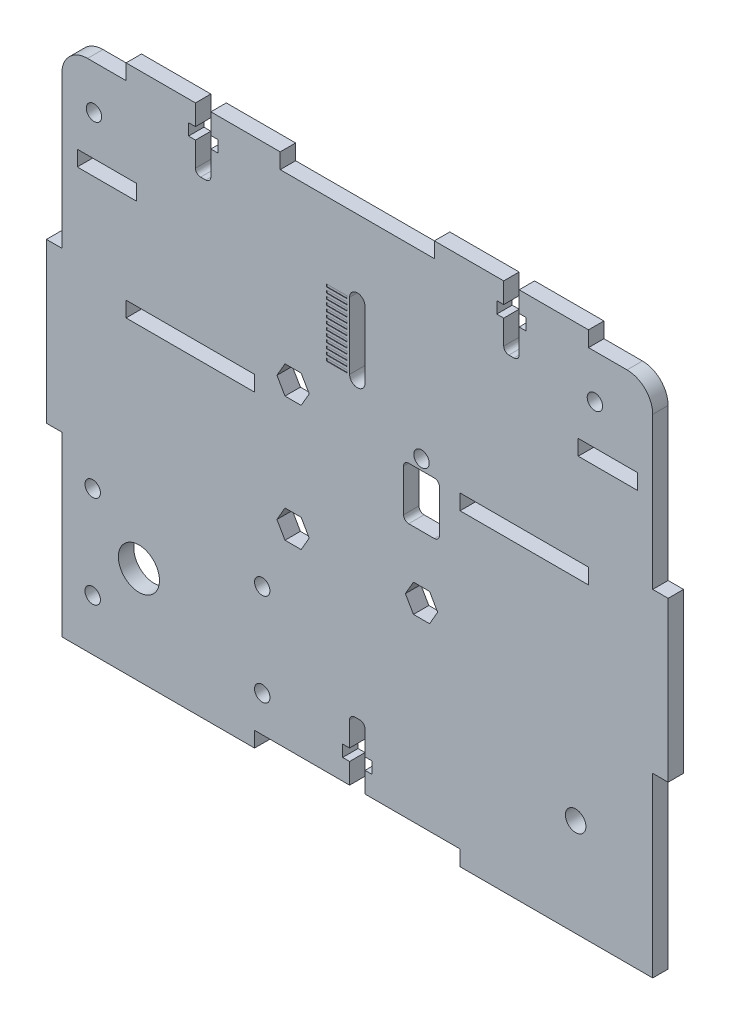
SolidWorks part; units mm, degrees
other "Marcação1"
sketch "Esboço7" plane through (-68, 31.5, 3) normal (-0.6758, 0.2828, 0.6807) x (0.7271, 0.1043, 0.6785)
sketch "Esboço8" plane through (-68, 31.5, 3) normal (-0.6758, 0.2828, 0.6807) x (0.7271, 0.1043, 0.6785)
sketch "Esboço9" plane through (-68, 31.5, 3) normal (-0.6758, 0.2828, 0.6807) x (0.7271, 0.1043, 0.6785)
sketch "Esboço10" plane through (-68, 31.5, 3) normal (-0.6758, 0.2828, 0.6807) x (0.7271, 0.1043, 0.6785)
sketch "Esboço11" plane through (-68, 36.25, 3) normal (-0.6758, 0.2828, 0.6807) x (0.7271, 0.1043, 0.6785)
sketch "Esboço13" plane through (-68, 36.25, 3) normal (-0.6758, 0.2828, 0.6807) x (0.7271, 0.1043, 0.6785)
sketch "Esboço15" plane through (-68, 36.25, 3) normal (-0.6758, 0.2828, 0.6807) x (0.7271, 0.1043, 0.6785)
sketch "Esboço19" plane through (-68, 66.25, 3) normal (-0.6758, 0.2828, 0.6807) x (0.7271, 0.1043, 0.6785)
sketch "Esboço22" plane through (-68, 95.5577, 3) normal (-0.6758, 0.2828, 0.6807) x (0.7271, 0.1043, 0.6785)
sketch "Sketch18" plane through (-60.5, 53, 1.5) normal (-0.6758, 0.2828, 0.6807) x (0.7271, 0.1043, 0.6785)
sketch "Sketch19" plane through (-60.5, 53, 1.5) normal (-0.6758, 0.2828, 0.6807) x (0.7271, 0.1043, 0.6785)
sketch "Sketch21" plane through (-60.5, 53, 1.5) normal (-0.6758, 0.2828, 0.6807) x (0.7271, 0.1043, 0.6785)
material "Acrylic (Medium-high impact)"
ref_plane "Plano frontal" through (0, 0, 0) normal (0, 0, 1) x (1, 0, 0)
ref_plane "Plano superior" through (0, 0, 0) normal (0, 1, 0) x (1, 0, 0)
ref_plane "Plano direito" through (0, 0, 0) normal (1, 0, 0) x (0, 0, -1)
sketch "Esboço1" plane through (0, 0, 0) normal (0, 0, 1) x (1, 0, 0)
  line L6 (57.5, -50) -> (-57.5, -50)
  line L8 (57.5, -50) -> (57.5, 50)
  line L9 (57.5, 50) -> (-57.5, 50)
  line L10 (-57.5, -50) -> (-57.5, 50)
  line L11 (57.5, -50) -> (-57.5, 50) construction
  line L12 (57.5, 50) -> (-57.5, -50) construction
  point P0 (0, 0)
  dimension "D1" = 100
  dimension "D2" = 115
extrude "Ressalto-extrusão1" add sketch "Esboço1" along normal mid plane 3
sketch "Esboço2" plane through (0, 0, 1.5) normal (0, 0, 1) x (1, 0, 0)
  line L1 (-20, -50) -> (20, -50)
  line L2 (-20, -50) -> (-20, -47)
  line L3 (-20, -47) -> (20, -47)
  line L4 (20, -50) -> (20, -47)
  line L6 (-57.5, -50) -> (57.5, -50) construction
  line L25 (57.5, 50) -> (-57.5, 50) construction
  line L26 (-45, 13) -> (-20, 13)
  line L29 (-45, 13) -> (-45, 10)
  line L30 (-45, 10) -> (-20, 10)
  line L31 (-20, 13) -> (-20, 10)
  line L32 (0, -1.65) -> (0, 1.65) construction
  line L33 (20, 13) -> (20, 10)
  line L34 (45, 10) -> (20, 10)
  line L35 (45, 13) -> (45, 10)
  line L36 (45, 13) -> (20, 13)
  point P6 (0, -47)
  dimension "D4" = 3
  dimension "D5" = 40
  dimension "D1" = 37
  dimension "D2" = 40
  dimension "D3" = 25
extrude "Corte-extrusão1" cut sketch "Esboço2" against normal through all
sketch "Esboço3" plane through (0, 0, 1.5) normal (0, 0, 1) x (1, 0, 0)
  line L0 (57.5, -50) -> (57.5, 50) construction
  line L1 (57.5, 15.5) -> (60.5, 15.5)
  line L2 (57.5, 15.5) -> (57.5, -15.5)
  line L3 (57.5, -15.5) -> (60.5, -15.5)
  line L4 (60.5, 15.5) -> (60.5, -15.5)
  line L5 (0, -1.65) -> (0, 1.65) construction
  line L6 (-57.5, -15.5) -> (-60.5, -15.5)
  line L7 (-57.5, 15.5) -> (-60.5, 15.5)
  line L8 (-57.5, 15.5) -> (-57.5, -15.5)
  line L9 (-60.5, 15.5) -> (-60.5, -15.5)
  line L10 (57.5, 50) -> (-57.5, 50) construction
  line L11 (-45, 53) -> (-15, 53)
  line L12 (-45, 53) -> (-45, 50)
  line L13 (-45, 50) -> (-15, 50)
  line L14 (-15, 53) -> (-15, 50)
  line L15 (15, 53) -> (15, 50)
  line L16 (45, 50) -> (15, 50)
  line L17 (45, 53) -> (45, 50)
  line L18 (45, 53) -> (15, 53)
  line L19 (0, -37.5) -> (0, 37.5) construction
  line L20 (-57.5, 50) -> (-57.5, -50) construction
  point P6 (57.5, 0)
  point P28 (0, 0)
  dimension "D1" = 3
  dimension "D2" = 31
  dimension "D3" = 3
  dimension "D4" = 30
  dimension "D5" = 12.5
  dimension "D6" = 15
extrude "Ressalto-extrusão2" add sketch "Esboço3" against normal through all
sketch "Esboço30" plane through (0, 0, -1.5) normal (0, 0, -1) x (-1, 0, 0)
  line L0 (60.5, 15.5) -> (60.5, -15.5) construction
  line L1 (57.5, -50) -> (20, -50) construction
  circle A0 centre (42.5, -31) radius 4
  dimension "D1" = 8
  dimension "D2" = 18
  dimension "D3" = 19
extrude "Corte-extrusão11" cut sketch "Esboço30" against normal through all both and the other way through all
sketch "Esboço31" plane through (0, 0, -1.5) normal (0, 0, -1) x (-1, 0, 0)
  circle A4 centre (51.5, -22) radius 1.5
  circle A5 centre (51.5, -40) radius 1.5
  circle A6 centre (42.5, -31) radius 4 construction
  circle A7 centre (18.5, -22) radius 1.5
  circle A8 centre (18.5, -40) radius 1.5
  dimension "D1" = 3
  dimension "D2" = 9
  dimension "D3" = 9
  dimension "D4" = 18
  dimension "D5" = 33
extrude "Corte-extrusão12" cut sketch "Esboço31" against normal through all both and the other way through all
sketch "Esboço4" plane through (0, 0, 1.5) normal (0, 0, 1) x (1, 0, 0)
  line L0 (-46.5, -31) -> (-38.5, -31) construction
  line L61 (-57.5, -15.5) -> (-57.5, -50) construction
  line L65 (57.5, -50) -> (57.5, -15.5) construction
  circle A9 centre (-42.5, -31) radius 4 construction
  circle A13 centre (42.5, -31) radius 2
  point P70 (-42.5, -31)
  dimension "D1" = 15
  dimension "D2" = 4
  dimension "D8" = 15
extrude "Corte-extrusão2" cut sketch "Esboço4" against normal through all
sketch "Sketch5" plane through (0, 0, 0) normal (0, 0, 1) x (1, 0, 0)
  line L0 (20, -47) -> (-20, -47) construction
  line L1 (-1.5, -47) -> (1.5, -47)
  line L2 (-1.5, -47) -> (-1.5, -43)
  line L3 (-0.5, -35) -> (0.5, -35)
  line L4 (1.5, -47) -> (1.5, -43)
  line L5 (1.5, -40.73) -> (2.85, -40.73)
  line L6 (-2.85, -40.73) -> (-1.5, -40.73)
  line L7 (-2.85, -40.73) -> (-2.85, -43)
  line L8 (-2.85, -43) -> (-1.5, -43)
  line L9 (2.85, -40.73) -> (2.85, -43)
  line L10 (-1.5, -40.73) -> (-1.5, -36)
  line L11 (1.5, -43) -> (2.85, -43)
  line L12 (1.5, -40.73) -> (1.5, -36)
  arc A0 (0.5, -35) -> (1.5, -36) centre (0.5, -36) cw
  arc A1 (-1.5, -36) -> (-0.5, -35) centre (-0.5, -36) cw
  point P6 (0, -35)
  point P18 (1.5, -35)
  point P21 (-1.5, -35)
  dimension "D7" = 1
  dimension "D1" = 12
  dimension "D2" = 3
  dimension "D3" = 2.27
  dimension "D4" = 1.35
  dimension "D5" = 1.35
  dimension "D6" = 4
extrude "Cut-Extrude2" cut sketch "Sketch5" against normal through all both and the other way through all
sketch "Sketch8" [suppressed] plane through (0, 0, 1.5) normal (0, 0, 1) x (1, 0, 0)
  line L8 (-57.5, 39.6519) -> (-53.4896, 39.6519)
  line L9 (-58, 31.6519) -> (-58, 23.6519) construction
  line L10 (-57.5, 23.6519) -> (-53.4896, 23.6519)
  line L11 (-45, 36.6519) -> (-45, 26.6519)
  line L12 (-58, 31.6519) -> (-45, 31.6519) construction
  line L13 (-48.5, 41.4019) -> (-50, 44)
  line L14 (-50, 44) -> (-53, 44)
  line L15 (-53, 44) -> (-54.5, 41.4019)
  line L16 (-54.5, 41.4019) -> (-53.4896, 39.6519)
  line L18 (-49.5104, 39.6519) -> (-48.5, 41.4019)
  line L19 (-49.5104, 39.6519) -> (-48, 39.6519)
  line L22 (-53.8581, 38.8038) -> (-52.2318, 38.8038) [skipped]
  line L24 (-49.5104, 23.6519) -> (-48.5, 21.9019)
  line L25 (-54.5, 21.9019) -> (-53.4896, 23.6519)
  line L26 (-53, 19.3038) -> (-54.5, 21.9019)
  line L27 (-50, 19.3038) -> (-53, 19.3038)
  line L28 (-48.5, 21.9019) -> (-50, 19.3038)
  line L29 (-45, 50) -> (-57.5, 50) construction
  line L30 (-57.5, 50) -> (-57.5, 15.5) construction
  line L31 (-57.5, 39.6519) -> (-57.5, 23.6519)
  line L32 (-58, 39.6519) -> (-58, 31.6519) construction
  line L33 (-58, 39.6519) -> (-57.5, 39.6519) construction
  line L34 (-58, 23.6519) -> (-57.5, 23.6519) construction
  line L35 (-49.5104, 23.6519) -> (-48, 23.6519)
  line L36 (0, -1.65) -> (0, 1.65) construction
  line L37 (58, 23.6519) -> (57.5, 23.6519) construction
  line L38 (58, 39.6519) -> (57.5, 39.6519) construction
  line L39 (58, 39.6519) -> (58, 31.6519) construction
  line L40 (58, 31.6519) -> (45, 31.6519) construction
  line L41 (58, 31.6519) -> (58, 23.6519) construction
  line L42 (49.5104, 23.6519) -> (48, 23.6519)
  line L43 (57.5, 39.6519) -> (57.5, 23.6519)
  line L44 (48.5, 21.9019) -> (50, 19.3038)
  line L45 (50, 19.3038) -> (53, 19.3038)
  line L46 (53, 19.3038) -> (54.5, 21.9019)
  line L47 (54.5, 21.9019) -> (53.4896, 23.6519)
  line L48 (49.5104, 23.6519) -> (48.5, 21.9019)
  line L49 (49.5104, 39.6519) -> (48, 39.6519)
  line L50 (49.5104, 39.6519) -> (48.5, 41.4019)
  line L51 (54.5, 41.4019) -> (53.4896, 39.6519)
  line L52 (53, 44) -> (54.5, 41.4019)
  line L53 (50, 44) -> (53, 44)
  line L54 (48.5, 41.4019) -> (50, 44)
  line L55 (45, 36.6519) -> (45, 26.6519)
  line L56 (57.5, 23.6519) -> (53.4896, 23.6519)
  line L57 (57.5, 39.6519) -> (53.4896, 39.6519)
  arc A0 (-49.25, 40.1029) -> (-53.75, 40.1029) centre (-51.5, 41.4019) ccw construction
  arc A1 (-49.25, 23.201) -> (-53.75, 23.201) centre (-51.5, 21.9019) cw construction
  arc A2 (-48, 23.6519) -> (-45, 26.6519) centre (-48, 26.6519) ccw
  arc A3 (-48, 39.6519) -> (-45, 36.6519) centre (-48, 36.6519) cw
  arc A4 (49.25, 23.201) -> (53.75, 23.201) centre (51.5, 21.9019) ccw construction
  arc A5 (49.25, 40.1029) -> (53.75, 40.1029) centre (51.5, 41.4019) cw construction
  arc A6 (48, 39.6519) -> (45, 36.6519) centre (48, 36.6519) ccw
  arc A7 (48, 23.6519) -> (45, 26.6519) centre (48, 26.6519) cw
  point P27 (-51.5, 31.6519)
  point P36 (-45, 23.6519)
  point P39 (-45, 39.6519)
  point P72 (45, 39.6519)
  point P73 (45, 23.6519)
  dimension "D1" = 13
  dimension "D3" = 3
  dimension "D5" = 6
  dimension "D4" = 19.5
  dimension "D6" = 3
  dimension "D7" = 3
  dimension "D8" = 16
extrude "Cut-Extrude6" [suppressed] cut sketch "Sketch8" against normal through all both and the other way through all
fillet "Fillet2" [suppressed] radius 1.5
sketch "Sketch17" plane through (0, 0, 0) normal (0, 0, 1) x (1, 0, 0)
  line L1 (-54.5, 33.7) -> (-43, 33.7)
  line L2 (-54.5, 33.7) -> (-54.5, 30.7)
  line L3 (-54.5, 30.7) -> (-43, 30.7)
  line L4 (-43, 33.7) -> (-43, 30.7)
  line L5 (-45, 50) -> (-57.5, 50) construction
  line L6 (-57.5, 50) -> (-57.5, 15.5) construction
  line L7 (0, -1.65) -> (0, 1.65) construction
  line L8 (43, 33.7) -> (43, 30.7)
  line L9 (54.5, 30.7) -> (43, 30.7)
  line L10 (54.5, 33.7) -> (54.5, 30.7)
  line L11 (54.5, 33.7) -> (43, 33.7)
  circle A0 centre (-51.25, 41.5) radius 1.5
  circle A1 centre (46.25, 41.5) radius 1.5
  point P6 (-48.75, 33.7)
  point P20 (48.75, 33.7)
  dimension "D2" = 3
  dimension "D5" = 7.8
  dimension "D6" = 7
  dimension "D1" = 11.5
  dimension "D3" = 3
  dimension "D4" = 2.5
  dimension "D7" = 3
  dimension "D8" = 2.5
  dimension "D9" = 86
extrude "Corte Gy-53LDK" cut sketch "Sketch17" against normal through all both and the other way through all
sketch "Sketch11" plane through (0, 0, 0) normal (0, 0, 1) x (1, 0, 0)
  line L0 (-15, 53) -> (-45, 53) construction
  line L1 (-31.5, 53) -> (-28.5, 53)
  line L2 (-31.5, 53) -> (-31.5, 49)
  line L3 (-30.5, 41) -> (-29.5, 41)
  line L4 (-28.5, 53) -> (-28.5, 49)
  line L5 (-45, 53) -> (-45, 50) construction
  line L6 (-28.5, 49) -> (-27.15, 49)
  line L7 (-32.85, 49) -> (-31.5, 49)
  line L8 (-32.85, 49) -> (-32.85, 46.73)
  line L9 (-32.85, 46.73) -> (-31.5, 46.73)
  line L10 (-27.15, 49) -> (-27.15, 46.73)
  line L11 (-31.5, 46.73) -> (-31.5, 42)
  line L12 (-28.5, 46.73) -> (-28.5, 42)
  line L13 (-28.5, 46.73) -> (-27.15, 46.73)
  line L14 (0, -1.65) -> (0, 1.65) construction
  line L15 (28.5, 46.73) -> (27.15, 46.73)
  line L16 (28.5, 46.73) -> (28.5, 42)
  line L17 (31.5, 46.73) -> (31.5, 42)
  line L18 (27.15, 49) -> (27.15, 46.73)
  line L19 (32.85, 46.73) -> (31.5, 46.73)
  line L20 (32.85, 49) -> (32.85, 46.73)
  line L21 (32.85, 49) -> (31.5, 49)
  line L22 (28.5, 49) -> (27.15, 49)
  line L23 (28.5, 53) -> (28.5, 49)
  line L24 (30.5, 41) -> (29.5, 41)
  line L25 (31.5, 53) -> (31.5, 49)
  line L26 (31.5, 53) -> (28.5, 53)
  arc A0 (-29.5, 41) -> (-28.5, 42) centre (-29.5, 42) ccw
  arc A1 (-31.5, 42) -> (-30.5, 41) centre (-30.5, 42) ccw
  arc A2 (31.5, 42) -> (30.5, 41) centre (30.5, 42) cw
  arc A3 (29.5, 41) -> (28.5, 42) centre (29.5, 42) cw
  point P12 (-31.5, 41)
  point P39 (31.5, 41)
  dimension "D4" = 1
  dimension "D1" = 3
  dimension "D2" = 12
  dimension "D3" = 13.5
  dimension "D5" = 4
  dimension "D6" = 2.27
  dimension "D7" = 1.35
  dimension "D8" = 1.35
extrude "Cut-Extrude8" cut sketch "Sketch11" against normal through all both and the other way through all
sketch "Sketch16" plane through (0, 0, 0) normal (0, 0, 1) x (1, 0, 0)
  line L3 (15.64, -9.2807) -> (14.07, -6.5614)
  line L4 (10, 13.0193) -> (15, 13.0193)
  line L5 (9, 12.0193) -> (9, 3.8193)
  line L6 (10, 2.8193) -> (15, 2.8193)
  line L7 (16, 12.0193) -> (16, 3.8193)
  line L8 (14.07, -6.5614) -> (10.93, -6.5614)
  line L9 (10.93, -6.5614) -> (9.36, -9.2807)
  line L10 (9.36, -9.2807) -> (10.93, -12)
  line L11 (10.93, -12) -> (14.07, -12)
  line L12 (14.07, -12) -> (15.64, -9.2807)
  line L14 (-9.36, 15.0193) -> (-10.93, 17.7386)
  line L15 (-10.93, 17.7386) -> (-14.07, 17.7386)
  line L16 (-14.07, 17.7386) -> (-15.64, 15.0193)
  line L17 (-15.64, 15.0193) -> (-14.07, 12.3)
  line L18 (-14.07, 12.3) -> (-10.93, 12.3)
  line L19 (-10.93, 12.3) -> (-9.36, 15.0193)
  line L20 (-9.36, -9.2807) -> (-10.93, -6.5614)
  line L21 (-10.93, -6.5614) -> (-14.07, -6.5614)
  line L22 (-14.07, -6.5614) -> (-15.64, -9.2807)
  line L23 (-15.64, -9.2807) -> (-14.07, -12)
  line L24 (-14.07, -12) -> (-10.93, -12)
  line L25 (-10.93, -12) -> (-9.36, -9.2807)
  line L26 (-12.5, 15.0193) -> (12.5, 15.0193) construction
  line L27 (15, 50) -> (-15, 50) construction
  circle A0 centre (-12.5, 15.0193) radius 1.5 construction
  circle A1 centre (12.5, 15.0193) radius 1.5
  circle A2 centre (-12.5, -9.2807) radius 1.5 construction
  circle A3 centre (12.5, -9.2807) radius 1.5 construction
  arc A4 (9, 3.8193) -> (10, 2.8193) centre (10, 3.8193) ccw
  arc A5 (15, 2.8193) -> (16, 3.8193) centre (15, 3.8193) ccw
  arc A6 (15, 13.0193) -> (16, 12.0193) centre (15, 12.0193) cw
  arc A7 (10, 13.0193) -> (9, 12.0193) centre (10, 12.0193) ccw
  circle A8 centre (12.5, -9.2807) radius 2.7193 construction
  circle A9 centre (-12.5, 15.0193) radius 2.7193 construction
  circle A10 centre (-12.5, -9.2807) radius 2.7193 construction
  circle A11 centre (-18.5, -22) radius 1.5 construction
  point P8 (12.5, 13.0193)
  point P14 (0, 15.0193)
  point P21 (16, 2.8193)
  point P24 (16, 13.0193)
  dimension "D1" = 3
  dimension "D2" = 25
  dimension "D3" = 24.3
  dimension "D4" = 8.5
  dimension "D7" = 2
  dimension "D9" = 1
  dimension "D6" = 0.5
  dimension "D8" = 10.2
  dimension "D10" = 3.14
  dimension "D11" = 3.14
  dimension "D12" = 3.14
extrude "Cut-Extrude12" cut sketch "Sketch16" against normal through all both and the other way through all
sketch "Sketch12" plane through (0, 0, 1.5) normal (0, 0, 1) x (1, 0, 0)
  line L2 (-6, 23.7803) -> (-2, 23.7803)
  line L4 (0, 22.2386) -> (0, 35.2386) construction
  line L7 (-1.5, 22.2386) -> (-1.5, 35.2386)
  line L8 (1.5, 22.2386) -> (1.5, 35.2386)
  line L9 (-6, 22.7386) -> (-2, 22.7386)
  line L10 (-6, 22.7386) -> (-6, 22.2386)
  line L11 (-6, 22.2386) -> (-2, 22.2386)
  line L12 (-2, 22.7386) -> (-2, 22.2386)
  line L13 (-6, 23.7803) -> (-6, 23.2803)
  line L14 (-6, 23.2803) -> (-2, 23.2803)
  line L15 (-2, 23.7803) -> (-2, 23.2803)
  line L16 (-6, 24.822) -> (-2, 24.822)
  line L17 (-6, 24.822) -> (-6, 24.322)
  line L18 (-6, 24.322) -> (-2, 24.322)
  line L19 (-2, 24.822) -> (-2, 24.322)
  line L20 (-6, 25.8636) -> (-2, 25.8636)
  line L21 (-6, 25.8636) -> (-6, 25.3636)
  line L22 (-6, 25.3636) -> (-2, 25.3636)
  line L23 (-2, 25.8636) -> (-2, 25.3636)
  line L24 (-6, 26.9053) -> (-2, 26.9053)
  line L25 (-6, 26.9053) -> (-6, 26.4053)
  line L26 (-6, 26.4053) -> (-2, 26.4053)
  line L27 (-2, 26.9053) -> (-2, 26.4053)
  line L28 (-6, 27.947) -> (-2, 27.947)
  line L29 (-6, 27.947) -> (-6, 27.447)
  line L30 (-6, 27.447) -> (-2, 27.447)
  line L31 (-2, 27.947) -> (-2, 27.447)
  line L32 (-6, 28.9886) -> (-2, 28.9886)
  line L33 (-6, 28.9886) -> (-6, 28.4886)
  line L34 (-6, 28.4886) -> (-2, 28.4886)
  line L35 (-2, 28.9886) -> (-2, 28.4886)
  line L36 (-6, 30.0303) -> (-2, 30.0303)
  line L37 (-6, 30.0303) -> (-6, 29.5303)
  line L38 (-6, 29.5303) -> (-2, 29.5303)
  line L39 (-2, 30.0303) -> (-2, 29.5303)
  line L40 (-6, 31.072) -> (-2, 31.072)
  line L41 (-6, 31.072) -> (-6, 30.572)
  line L42 (-6, 30.572) -> (-2, 30.572)
  line L43 (-2, 31.072) -> (-2, 30.572)
  line L44 (-6, 32.1136) -> (-2, 32.1136)
  line L45 (-6, 32.1136) -> (-6, 31.6136)
  line L46 (-6, 31.6136) -> (-2, 31.6136)
  line L47 (-2, 32.1136) -> (-2, 31.6136)
  line L48 (-6, 33.1553) -> (-2, 33.1553)
  line L49 (-6, 33.1553) -> (-6, 32.6553)
  line L50 (-6, 32.6553) -> (-2, 32.6553)
  line L51 (-2, 33.1553) -> (-2, 32.6553)
  line L52 (-6, 34.197) -> (-2, 34.197)
  line L53 (-6, 34.197) -> (-6, 33.697)
  line L54 (-6, 33.697) -> (-2, 33.697)
  line L55 (-2, 34.197) -> (-2, 33.697)
  line L56 (-6, 35.2386) -> (-2, 35.2386)
  line L57 (-6, 35.2386) -> (-6, 34.7386)
  line L58 (-6, 34.7386) -> (-2, 34.7386)
  line L59 (-2, 35.2386) -> (-2, 34.7386)
  line L61 (-10.93, 17.7386) -> (-14.07, 17.7386) construction
  circle A1 centre (0, 22.2386) radius 1.5 construction
  arc A4 (-1.5, 22.2386) -> (1.5, 22.2386) centre (0, 22.2386) ccw
  arc A5 (1.5, 35.2386) -> (-1.5, 35.2386) centre (0, 35.2386) ccw
  point P6 (0, 28.7386)
  dimension "D1" = 3
  dimension "D2" = 3
  dimension "D3" = 13
  dimension "D4" = 0.5
  dimension "D5" = 4
  dimension "D6" = 0.5
  dimension "D7" = 13
extrude "Cut-Extrude9" cut sketch "Sketch12" against normal through all contours L8 A5 L7 A4 | A5 L8 A4 L7 region at (0, 28.7386, 1.5)
fillet "Fillet1" radius 5 2 edges at (-57.5, 50, 0) (57.5, 50, 0)
extrude "Cut-Extrude13" cut sketch "Sketch12<4>" against normal blind 0.1 contours L52 L55 L54 L53 | L48 L51 L50 L49 | L40 L43 L42 L41 | L36 L39 L38 L37 | L24 L27 L26 L25 | L16 L19 L18 L17 | L59 L56 L57 L58 | L55 L52 L53 L54 | L51 L48 L49 L50 | L47 L44 L45 L46 | L43 L40 L41 L42 | L39 L36 L37 L38 | L35 L32 L33 L34 | L31 L28 L29 L30 | L27 L24 L25 L26 | L23 L20 L21 L22 | L19 L16 L17 L18 | L15 L2 L13 L14 | L12 L9 L10 L11 region at (-4, 23.5303, 1.5) region at (-4, 22.4886, 1.5) region at (-4, 24.572, 1.5) region at (-4, 25.6136, 1.5) region at (-4, 26.6553, 1.5) region at (-4, 27.697, 1.5) region at (-4, 28.7386, 1.5) region at (-4, 29.7803, 1.5) region at (-4, 30.822, 1.5) region at (-4, 31.8636, 1.5) region at (-4, 32.9053, 1.5) region at (-4, 33.947, 1.5) region at (-4, 34.9886, 1.5)
sketch "Sketch12<4>" plane through (0, 0, 1.5) normal (0, 0, 1) x (1, 0, 0) same geometry as "Sketch12"
